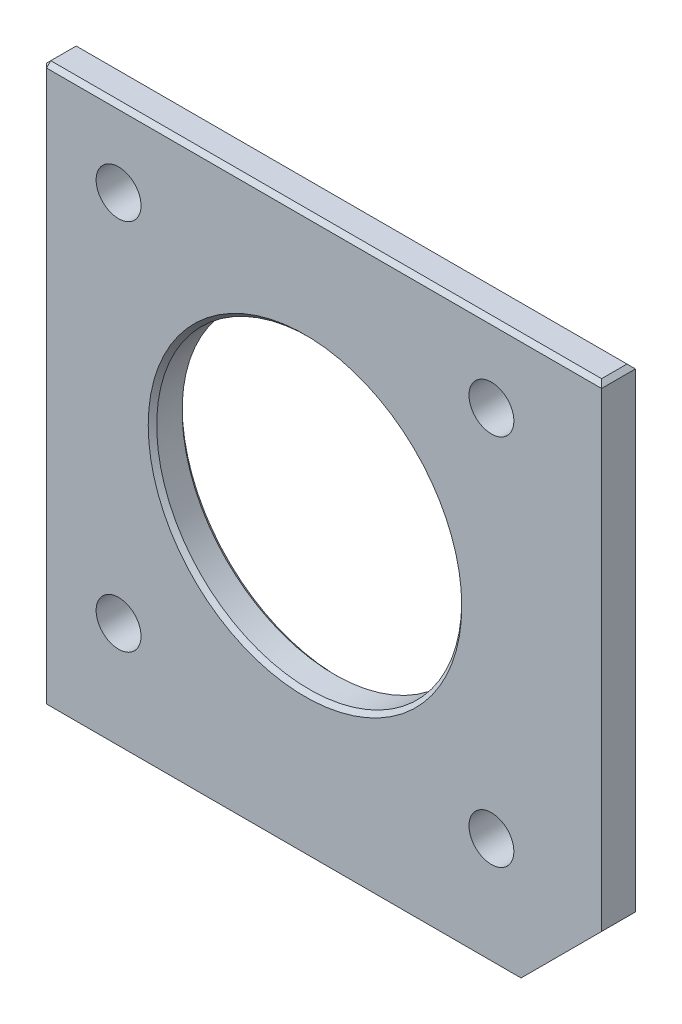
SolidWorks part; units mm, degrees
material "AISI 1020"
ref_plane "Plan de face" through (0, 0, 0) normal (0, 0, 1) x (1, 0, 0)
ref_plane "Plan de dessus" through (0, 0, 0) normal (0, 1, 0) x (1, 0, 0)
ref_plane "Plan de droite" through (0, 0, 0) normal (1, 0, 0) x (0, 0, -1)
sketch "Esquisse1" plane through (0, 0, 0) normal (0, 0, 1) x (1, 0, 0)
  line L1 (-33, 33) -> (33, 33)
  line L2 (-33, 33) -> (-33, -33)
  line L3 (-33, -33) -> (33, -33)
  line L4 (33, 33) -> (33, -33)
  line L5 (-33, 33) -> (33, -33) construction
  line L6 (-33, -33) -> (33, 33) construction
  circle A0 centre (-2, 2) radius 18
  point P0 (0, 0)
  dimension "D5" = 36
  dimension "D1" = 66
  dimension "D2" = 66
  dimension "D3" = 31
  dimension "D4" = 31
extrude "Boss.-Extru.1" add sketch "Esquisse1" along normal blind 4
chamfer "Chanfrein1" distance 10 angle 45 1 edges at (33, -33, 2)
chamfer "Chanfrein2" distance 0.5 angle 45 11 edges at (-33, 0, 4) (-33, -33, 2) (-33, 0, 0) (33, 33, 2) (0, 33, 4) (-33, 33, 2) (0, 33, 0) (16, 2, 0) (16, 2, 4) (-5, -33, 0) (-5, -33, 4)
ref_axis "Axe1" through (-2, 2, 3.5) along (0, 0, -1)
hole_wizard "Dégagement M51" positions "Esquisse4" profile "Esquisse5" hole size "M5" standard "ISO" end condition through all
sketch "Esquisse4" plane through (0, 0, 4) normal (0, 0, 1) x (1, 0, 0)
  line L0 (-2, 36.13) -> (-2, -39.678) construction
  line L2 (-51.0745, 2) -> (55.9664, 2) construction
  point P0 (-24, 24)
  point P2 (20, 24)
  point P4 (20, -20)
  point P6 (-24, -20)
  point P18 (-162.0986, 40.1062)
  point P20 (-166.139, 40.1062)
  dimension "D1" = 44
  dimension "D2" = 44
sketch "Esquisse5" plane through (-24, 24, 4) normal (1, 0, 0) x (0, -1, 0)
  line L0 (0, 0) -> (0, 4)
  line L1 (0, 4) -> (2.65, 4)
  line L2 (2.65, 4) -> (2.65, 0)
  line L5 (2.65, 0) -> (0, 0)
  line L11 (0, -6.35) -> (0, 107.95) construction
  dimension "Diamètre du perçage jusqu'au prochain" = 5.3
  dimension "Profondeur du perçage jusqu'au prochain" = 4
